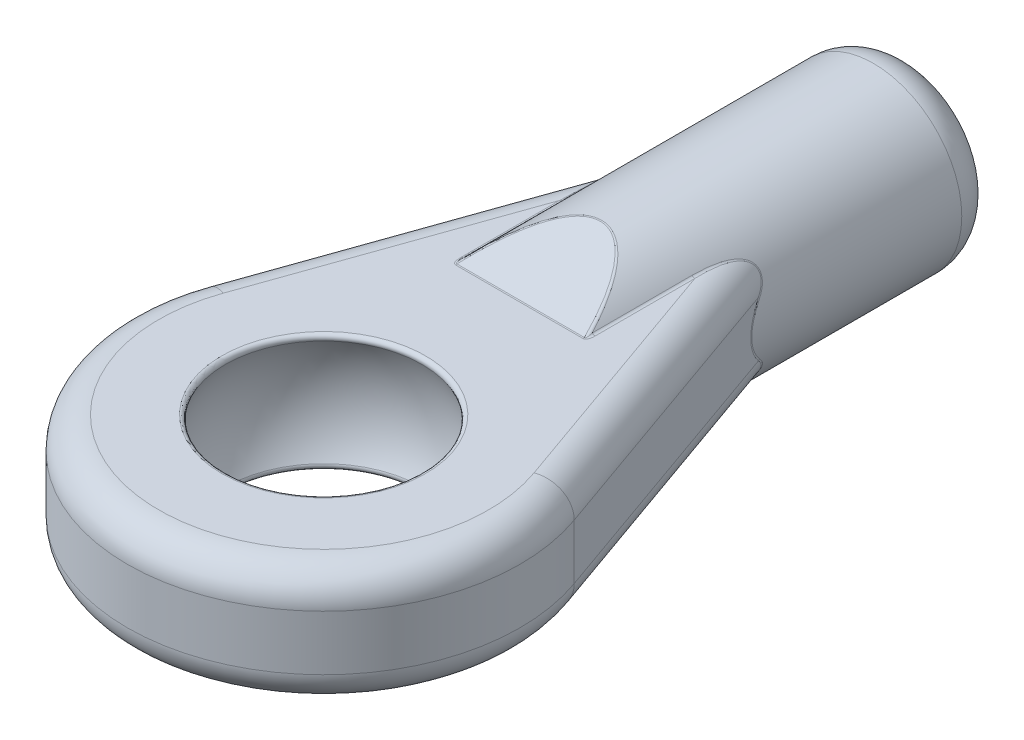
SolidWorks part; units mm, degrees
material "ABS"
ref_plane "Front Plane" through (0, 0, 0) normal (0, 0, 1) x (1, 0, 0)
ref_plane "Top Plane" through (0, 0, 0) normal (0, 1, 0) x (1, 0, 0)
ref_plane "Right Plane" through (0, 0, 0) normal (1, 0, 0) x (0, 0, -1)
sketch "Sketch1" plane through (0, 0, 0) normal (0, 1, 0) x (1, 0, 0)
  circle A0 centre (0, 0) radius 5
  dimension "D1" = 10
extrude "Boss-Extrude1" add sketch "Sketch1" along normal mid plane 3
ref_plane "Plane1" through (0, 0, -5) normal (0, 0, -1) x (-1, 0, 0)
ref_plane "Plane2" through (0, 0, 5) normal (0, 0, 1) x (1, 0, 0)
sketch "Sketch3" plane through (0, 0, -5) normal (0, 0, -1) x (-1, 0, 0)
  circle A0 centre (0, 0) radius 2.25
  dimension "D1" = 4.5
extrude "Boss-Extrude2" add sketch "Sketch3" along normal offset from surface (10 mm away) 20 separate body up to plane "Plane2" offset beyond the face yes
sketch "Sketch4" plane through (0, 0, 0) normal (0, 1, 0) x (1, 0, 0)
  line L0 (-4.714, 1.6667) -> (0, 15)
  line L1 (2.25, 15) -> (-2.25, 15) construction
  line L2 (0, 15) -> (4.714, 1.6667)
  line L3 (4.714, 1.6667) -> (-4.714, 1.6667)
  circle A0 centre (0, 0) radius 5 construction
extrude "Boss-Extrude3" add sketch "Sketch4" along normal mid plane 3
sketch "Sketch2" plane through (0, 0, 0) normal (0, 0, 1) x (1, 0, 0)
  line L0 (0, 0) -> (0, 50000) construction
  line L1 (0, 2.85) -> (0, -2.85)
  arc A0 (0, -2.85) -> (0, 2.85) centre (0, 0) ccw
  dimension "D1" = 5.7
revolve "Cut-Revolve1" cut sketch "Sketch2" angle 360 about L0
fillet "Fillet2" radius 0.8 6 edges at (-3.1955, 1.5, -5.9616) (3.1955, 1.5, -5.9616) (-3.1955, -1.5, -5.9616) (3.1955, -1.5, -5.9616) (0, 1.5, 5) (0, -1.5, 5)
sketch "Sketch5" plane through (0, 0, 0) normal (1, 0, 0) x (0, 0, -1)
  line L0 (5, 1.5) -> (7.0606, 2.25)
  line L1 (15, 2.25) -> (5, 2.25) construction
  line L2 (7.0606, 2.25) -> (5, 2.25)
  line L3 (5, 2.25) -> (5, 1.5) construction
  line L4 (5, 2.25) -> (5, 1.5)
  dimension "D1" = 20
extrude "Cut-Extrude1" cut sketch "Sketch5" against normal up to next and the other way up to next
mirror "Mirror1" about plane through (0, 0, 0) normal (0, 1, 0) of "Cut-Extrude1"
fillet "Fillet3" radius 1 1 edges at (2.25, 0, -15)
fillet "Fillet4" radius 0.1 14 edges at (2.25, 0, -8.636) (1.8981, -1.2082, -9.0849) (1.9089, 1.1911, -9.0955) (1.6771, -1.5, -6.4283) (1.6771, 1.5, -6.4283) (-1.6771, -1.5, -6.4283) (-1.9089, -1.1911, -9.0955) (-2.25, 0, -8.636) (-1.6771, 1.5, -6.4283) (0, -2.25, -7.0606) (0, -1.5, -5) (0, 2.25, -7.0606) (0, 1.5, -5) (-1.8981, 1.2082, -9.0849)
sketch "Sketch6" plane through (0, 0, -15) normal (0, 0, -1) x (-1, 0, 0)
  circle A0 centre (0, 0) radius 1.5
  dimension "D1" = 3
extrude "Cut-Extrude2" cut sketch "Sketch6" against normal blind 7
fillet "Fillet5" radius 0.1 2 edges at (0, -1.5, 2.4233) (0, 1.5, 2.4233)
